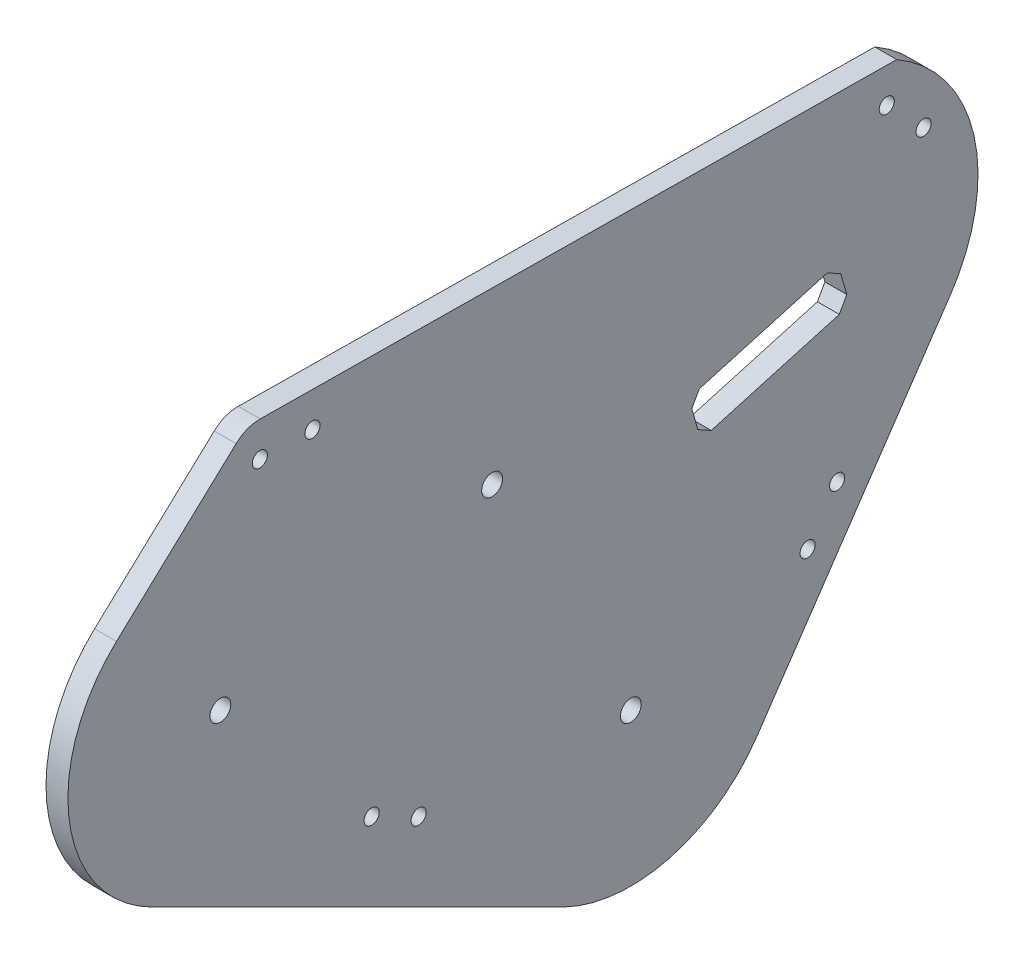
SolidWorks part; units mm, degrees
material "Beech"
ref_plane "Front" through (0, 0, 0) normal (0, 0, 1) x (1, 0, 0)
ref_plane "Top" through (0, 0, 0) normal (0, 1, 0) x (1, 0, 0)
ref_plane "Right" through (0, 0, 0) normal (1, 0, 0) x (0, 0, -1)
ref_axis "side-side" through (80.9, 0, 0) along (-1, 0, 0)
ref_axis "up-down" through (0, 50, 0) along (0, -1, 0)
ref_axis "front-back" through (0, 0, -80.9) along (0, 0, 1)
sketch "Sketch1" plane through (0, 0, 0) normal (1, 0, 0) x (0, 0, -1)
  line L1 (-490.5663, -59.5775) -> (-476.359, -66.6793)
  line L18 (-378.0756, 0.5453) -> (-381.2121, 2.2917)
  line L19 (-381.2121, 2.2917) -> (-410.5303, -6.0543)
  line L20 (-410.5303, -6.0543) -> (-412.2768, -9.1908)
  line L21 (-412.2768, -9.1908) -> (-410.8851, -14.0797)
  line L22 (-410.8851, -14.0797) -> (-407.7486, -15.8261)
  line L23 (-407.7486, -15.8261) -> (-378.4303, -7.4801)
  line L24 (-378.4303, -7.4801) -> (-376.6839, -4.3436)
  line L25 (-376.6839, -4.3436) -> (-378.0756, 0.5453)
  circle A1 centre (-519.7834, -15.0065) radius 4
  circle A3 centre (-457.7546, -1.4172) radius 4
  circle A5 centre (-426.0872, -61.8422) radius 4
  circle A10 centre (-510.7706, 30.1019) radius 7.9375 construction
  circle A13 centre (-394.4803, -6.7672) radius 4
  circle A14 centre (-367.6668, 28.5075) radius 7.9375 construction
  circle A16 centre (0, 0) radius 11.5
  circle A18 centre (-519.7834, -15.0065) radius 32.8041 construction
  circle A22 centre (-457.7546, -1.4172) radius 32.8041 construction
  circle A23 centre (-426.0872, -61.8422) radius 32.8041 construction
  circle A26 centre (-394.4803, -6.7672) radius 32.8041 construction
  circle A27 centre (-379.0063, -40.2511) radius 7.9375 construction
  arc A29 (-476.359, -66.6793) -> (-465.6263, -63.1004) centre (-472.7821, -59.5235) ccw
  arc A30 (-494.1451, -48.8447) -> (-490.5663, -59.5775) centre (-486.9894, -52.4217) ccw
sketch "Sketch3" plane through (0, 0, 0) normal (1, 0, 0) x (0, 0, -1)
  line L0 (-519.7834, -15.0065) -> (-478.2077, -5.8981) construction
  line L1 (-519.7834, -15.0065) -> (-510.8387, -19.4777) construction
  line L2 (-510.8387, -19.4777) -> (-508.6986, -29.246) construction
  line L3 (-508.6986, -29.246) -> (-506.745, -28.818) construction
  line L4 (-519.7834, -15.0065) -> (-506.745, -28.818) construction
  line L9 (-526.5522, -0.4362) -> (-533.9402, -7.4106) construction
  line L18 (-457.7546, -1.4172) -> (-438.966, -1.0677) construction
  line L19 (-457.7546, -1.4172) -> (-468.5547, -3.7833) construction
  line L20 (-457.7546, -1.4172) -> (-458.1078, 17.5732) construction
  line L21 (-458.1078, 17.5732) -> (-462.1725, 36.1268) construction
  line L30 (-457.7546, -1.4172) -> (-462.1725, 36.1268) construction
  line L31 (-454.1042, -31.095) -> (-461.4049, 28.2606) construction
  line L32 (-426.0872, -61.8422) -> (-417.1425, -66.3134) construction
  line L33 (-426.0872, -61.8422) -> (-415.0303, -46.483) construction
  line L34 (-417.1425, -66.3134) -> (-409.0267, -72.1558) construction
  line L35 (-409.0267, -72.1558) -> (-410.1952, -73.779) construction
  line L36 (-426.0872, -61.8422) -> (-410.1952, -73.779) construction
  line L45 (-477.8497, -10.2828) -> (-374.3247, -113.4016) construction
  point P28 (-507.5781, -27.9355)
  line B0 (-533.8369, -3.8222) -> (-530.1406, -0.3328)
  line B1 (-533.9402, -7.4106) -> (-513.0146, -29.5768)
  line B2 (-526.5522, -0.4362) -> (-505.6267, -22.6024)
  line B3 (-509.4262, -29.6802) -> (-505.73, -26.1908)
  line B4 (-530.1406, -0.3328) -> (-526.5522, -0.4362)
  line B5 (-533.8369, -3.8222) -> (-533.9402, -7.4106)
  line B6 (-505.6267, -22.6024) -> (-505.73, -26.1908)
  line B7 (-513.0146, -29.5768) -> (-509.4262, -29.6802)
  line B8 (-533.9402, -7.4106) -> (-505.6267, -22.6024) construction
  dimension "D1" = 10
  dimension "D2" = 2
  dimension "D5" = 2
sketch_block_instance "Block2-1"
sketch_block "Block2" parameters "D1"=45
sketch "Sketch4" plane through (0, 0, 0) normal (1, 0, 0) x (0, 0, -1)
  line L0 (-360.5987, -33.6558) -> (-22.7158, -38.2073) construction
  line L1 (-510.6822, 38.0389) -> (-365.3775, 36.42)
  line L2 (-543.504, 10.4623) -> (-516.1804, 35.9104)
  line L3 (-510.7706, 30.1019) -> (-498.7714, 29.9682) construction
  line L8 (-397.2737, -81.3642) -> (-353.1807, -16.2849)
  line L9 (-368.0747, 36.4512) -> (-30.9445, 31.9099) construction
  line L10 (-441.6488, -92.9736) -> (-535.345, -46.1379)
  line L11 (-486.9894, -52.4217) -> (-472.7821, -59.5235) construction
  line L12 (-367.6668, 28.5075) -> (-359.2766, 19.9282) construction
  line L13 (-385.7372, -50.1857) -> (-379.0063, -40.2511) construction
  arc A0 (-543.504, 10.4623) -> (-535.345, -46.1379) centre (-519.7834, -15.0065) ccw
  arc A2 (-441.6488, -92.9736) -> (-397.2737, -81.3642) centre (-426.0872, -61.8422) ccw
  circle A5 centre (-379.0063, -40.2511) radius 7.9375 construction
  circle A7 centre (-394.4803, -6.7672) radius 32.8041 construction
  circle A8 centre (-367.6668, 28.5075) radius 7.9375 construction
  arc A10 (-22.7158, -38.2073) -> (-30.9445, 31.9099) centre (0, 0) ccw construction
  circle A11 centre (0, 0) radius 11.5 construction
  circle A12 centre (-426.0872, -61.8422) radius 32.8041 construction
  arc A14 (-481.3928, 24.128) -> (-445.2526, 31.064) centre (-457.7546, -1.4172) cw construction
  circle A15 centre (-457.7546, -1.4172) radius 32.8041 construction
  arc A17 (-360.5987, -33.6558) -> (-367.3302, -37.169) centre (-360.7064, -41.6551) ccw construction
  circle A18 centre (-485.2525, -53.2899) radius 1.7272
  circle A19 centre (-474.5189, -58.6553) radius 1.7272
  arc A22 (-360.3858, 0.2247) -> (-360.3847, 0.2196) centre (-394.4803, -6.7672) cw construction
  circle A23 centre (-367.6668, 28.5075) radius 7.9375 construction
  circle A24 centre (-510.7706, 30.1019) radius 7.9375 construction
  arc A25 (-510.6822, 38.0389) -> (-516.1804, 35.9104) centre (-510.7706, 30.1019) ccw
  circle A26 centre (-498.7714, 29.9682) radius 4 construction
  circle A27 centre (-498.7714, 29.9682) radius 7.9375 construction
  circle A29 centre (-510.7706, 30.1019) radius 1.7272
  circle A31 centre (-485.2525, -53.2899) radius 7.9375 construction
  circle A32 centre (-474.5189, -58.6553) radius 4 construction
  circle A33 centre (-498.7714, 29.9682) radius 1.7272
  circle A34 centre (-367.6668, 28.5075) radius 1.7272
  circle A35 centre (-359.2766, 19.9282) radius 1.7272
  circle A36 centre (-385.7372, -50.1857) radius 7.9375 construction
  circle A38 centre (-385.7372, -50.1857) radius 1.7272
  circle A39 centre (-379.0063, -40.2511) radius 1.7272
  circle A40 centre (-379.0063, -40.2511) radius 4 construction
  circle A42 centre (-394.4803, -6.7672) radius 34.8041 construction
  arc A44 (-353.1807, -16.2849) -> (-365.3775, 36.42) centre (-383.7257, 4.4102) ccw
  circle A45 centre (-359.2766, 19.9282) radius 4 construction
  circle A46 centre (-359.2766, 19.9282) radius 7.9375 construction
  point P50 (-479.8857, -55.9726)
  dimension "D1" = 2
  dimension "D2" = 31.4902
  dimension "D3" = 8
  dimension "D4" = 2
  dimension "D5" = 88.9
  dimension "D6" = 23
  dimension "D7" = 8
  dimension "D8" = 70
  dimension "D9" = 45
  dimension "D11" = 12
  dimension "D13" = 3.4544
  dimension "D17" = 8
  dimension "D18" = 2
  dimension "D20" = 8
  dimension "D10" = 12
  dimension "D12" = 6
  dimension "D14" = 12
  dimension "D15" = 12
  dimension "D16" = 42
extrude "Boss-Extrude1" add sketch "Sketch4" against normal blind 5
sketch "Sketch5" plane through (0, 0, 0) normal (1, 0, 0) x (0, 0, -1)
  line L0 (-533.9402, -7.4106) -> (-513.0146, -29.5768) construction
  line L1 (-454.1042, -31.095) -> (-461.4049, 28.2606) construction
  line L2 (-426.0872, -61.8422) -> (-410.1952, -73.779) construction
  line B0 (-533.8369, -3.8222) -> (-530.1406, -0.3328)
  line B1 (-533.9402, -7.4106) -> (-513.0146, -29.5768)
  line B2 (-526.5522, -0.4362) -> (-505.6267, -22.6024)
  line B3 (-509.4262, -29.6802) -> (-505.73, -26.1908)
  line B4 (-530.1406, -0.3328) -> (-526.5522, -0.4362)
  line B5 (-533.8369, -3.8222) -> (-533.9402, -7.4106)
  line B6 (-505.6267, -22.6024) -> (-505.73, -26.1908)
  line B7 (-513.0146, -29.5768) -> (-509.4262, -29.6802)
  line B8 (-533.9402, -7.4106) -> (-505.6267, -22.6024) construction
  line B9 (-453.0615, -18.7539) -> (-458.1065, -19.3745)
  line B10 (-450.8519, -15.9246) -> (-454.5732, 14.3305)
  line B11 (-460.9359, -17.1649) -> (-464.6572, 13.0902)
  line B12 (-457.4026, 16.5401) -> (-462.4477, 15.9196)
  line B13 (-458.1065, -19.3745) -> (-460.9359, -17.1649)
  line B14 (-453.0615, -18.7539) -> (-450.8519, -15.9246)
  line B15 (-464.6572, 13.0902) -> (-462.4477, 15.9196)
  line B16 (-454.5732, 14.3305) -> (-457.4026, 16.5401)
  line B17 (-450.8519, -15.9246) -> (-464.6572, 13.0902) construction
  line B18 (-384.1093, 17.78) -> (-379.0262, 17.78)
  line B19 (-386.6477, 15.2415) -> (-386.6477, -15.2415)
  line B20 (-376.4877, 15.2415) -> (-376.4877, -15.2415)
  line B21 (-384.1093, -17.78) -> (-379.0262, -17.78)
  line B22 (-379.0262, 17.78) -> (-376.4877, 15.2415)
  line B23 (-384.1093, 17.78) -> (-386.6477, 15.2415)
  line B24 (-376.4877, -15.2415) -> (-379.0262, -17.78)
  line B25 (-386.6477, -15.2415) -> (-384.1093, -17.78)
  line B26 (-386.6477, 15.2415) -> (-376.4877, -15.2415) construction
  line B27 (-441.83, -53.1962) -> (-438.7772, -49.1319)
  line B28 (-441.3248, -56.7504) -> (-416.9514, -75.0577)
  line B29 (-435.223, -48.6267) -> (-410.8496, -66.934)
  line B30 (-413.3972, -74.5525) -> (-410.3445, -70.4882)
  line B31 (-438.7772, -49.1319) -> (-435.223, -48.6267)
  line B32 (-441.83, -53.1962) -> (-441.3248, -56.7504)
  line B33 (-410.8496, -66.934) -> (-410.3445, -70.4882)
  line B34 (-416.9514, -75.0577) -> (-413.3972, -74.5525)
  line B35 (-441.3248, -56.7504) -> (-410.8496, -66.934) construction
  line B36 (-169.1424, 28.527) -> (-164.0593, 28.527)
  line B37 (-171.6808, 25.9885) -> (-171.6808, -4.4946)
  line B38 (-161.5208, 25.9885) -> (-161.5208, -4.4946)
  line B39 (-169.1424, -7.033) -> (-164.0593, -7.033)
  line B40 (-164.0593, 28.527) -> (-161.5208, 25.9885)
  line B41 (-169.1424, 28.527) -> (-171.6808, 25.9885)
  line B42 (-161.5208, -4.4946) -> (-164.0593, -7.033)
  line B43 (-171.6808, -4.4946) -> (-169.1424, -7.033)
  line B44 (-171.6808, 25.9885) -> (-161.5208, -4.4946) construction
  line B45 (-308.3006, 25.4927) -> (-303.2175, 25.4927)
  line B46 (-310.8391, 22.9543) -> (-310.8391, -7.5288)
  line B47 (-300.6791, 22.9543) -> (-300.6791, -7.5288)
  line B48 (-308.3006, -10.0673) -> (-303.2175, -10.0673)
  line B49 (-303.2175, 25.4927) -> (-300.6791, 22.9543)
  line B50 (-308.3006, 25.4927) -> (-310.8391, 22.9543)
  line B51 (-300.6791, -7.5288) -> (-303.2175, -10.0673)
  line B52 (-310.8391, -7.5288) -> (-308.3006, -10.0673)
  line B53 (-310.8391, 22.9543) -> (-300.6791, -7.5288) construction
  line B54 (-244.9639, 20.9416) -> (-239.8808, 20.9416)
  line B55 (-247.5024, 18.4032) -> (-247.5024, -12.0799)
  line B56 (-237.3424, 18.4032) -> (-237.3424, -12.0799)
  line B57 (-244.9639, -14.6184) -> (-239.8808, -14.6184)
  line B58 (-239.8808, 20.9416) -> (-237.3424, 18.4032)
  line B59 (-244.9639, 20.9416) -> (-247.5024, 18.4032)
  line B60 (-237.3424, -12.0799) -> (-239.8808, -14.6184)
  line B61 (-247.5024, -12.0799) -> (-244.9639, -14.6184)
  line B62 (-247.5024, 18.4032) -> (-237.3424, -12.0799) construction
  line B63 (-397.0219, 11.0128) -> (-391.9388, 11.0128)
  line B64 (-399.5603, 8.4744) -> (-399.5603, -22.0087)
  line B65 (-389.4003, 8.4744) -> (-389.4003, -22.0087)
  line B66 (-397.0219, -24.5472) -> (-391.9388, -24.5472)
  line B67 (-391.9388, 11.0128) -> (-389.4003, 8.4744)
  line B68 (-397.0219, 11.0128) -> (-399.5603, 8.4744)
  line B69 (-389.4003, -22.0087) -> (-391.9388, -24.5472)
  line B70 (-399.5603, -22.0087) -> (-397.0219, -24.5472)
  line B71 (-399.5603, 8.4744) -> (-389.4003, -22.0087) construction
sketch_block_instance "Block2-11"
sketch_block_instance "Block2-12"
sketch_block_instance "Block2-13"
sketch_block_instance "Block2-14"
sketch_block_instance "Block2-15"
sketch_block_instance "Block2-16"
sketch_block_instance "Block2-17"
sketch_block_instance "Block2-18"
extrude "Cut-Extrude2" [suppressed] cut sketch "Sketch5" against normal through all
sketch "Sketch6" plane through (0, 0, 0) normal (1, 0, 0) x (0, 0, -1)
  line L16 (-410.8002, -14.0124) -> (-407.7362, -15.7186)
  line L17 (-412.1693, -9.2032) -> (-410.8002, -14.0124)
  line L18 (-410.4631, -6.1392) -> (-412.1693, -9.2032)
  line L19 (-381.2245, 2.1842) -> (-410.4631, -6.1392)
  line L20 (-378.1604, 0.4781) -> (-381.2245, 2.1842)
  line L21 (-376.7914, -4.3311) -> (-378.1604, 0.4781)
  line L22 (-378.4975, -7.3952) -> (-376.7914, -4.3311)
  line L23 (-407.7362, -15.7186) -> (-378.4975, -7.3952)
  line L24 (-410.8002, -14.0124) -> (-407.7362, -15.7186)
  line L25 (-412.1693, -9.2032) -> (-410.8002, -14.0124)
  line L26 (-410.4631, -6.1392) -> (-412.1693, -9.2032)
  line L27 (-381.2245, 2.1842) -> (-410.4631, -6.1392)
  line L28 (-378.1604, 0.4781) -> (-381.2245, 2.1842)
  line L29 (-376.7914, -4.3311) -> (-378.1604, 0.4781)
  line L30 (-378.4975, -7.3952) -> (-376.7914, -4.3311)
  line L31 (-407.7362, -15.7186) -> (-378.4975, -7.3952)
  circle A0 centre (-519.7834, -15.0065) radius 2.3812
  circle A1 centre (-457.7546, -1.4172) radius 2.3813
  circle A2 centre (-394.4803, -6.7672) radius 2.3813 construction
  circle A3 centre (-426.0872, -61.8422) radius 2.3813
  dimension "D1" = 4.7625
  dimension "D2" = 0.1
extrude "Cut-Extrude3" cut sketch "Sketch6" against normal through all
